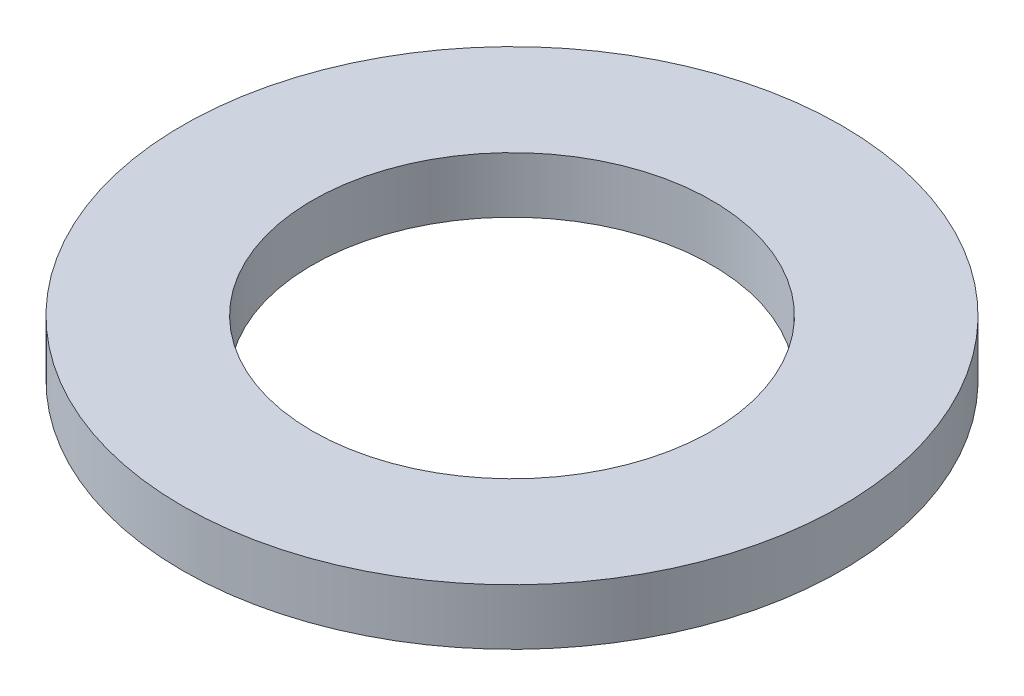
SolidWorks part; units mm, degrees
ref_plane "Front Plane" through (0, 0, 0) normal (0, 0, 1) x (1, 0, 0)
ref_plane "Top Plane" through (0, 0, 0) normal (0, 1, 0) x (1, 0, 0)
ref_plane "Right Plane" through (0, 0, 0) normal (1, 0, 0) x (0, 0, -1)
sketch "Sketch1" plane through (0, 0, 0) normal (0, 1, 0) x (1, 0, 0)
  circle A0 centre (0, 0) radius 82.5
  dimension "FLANGE_OD" = 165
extrude "Boss-Extrude1" add sketch "Sketch1" along normal blind 14
sketch "Sketch2" plane through (0, 0, 0) normal (0, 1, 0) x (1, 0, 0)
  circle A0 centre (0, 0) radius 50
  dimension "BORE_D" = 100
extrude "Cut-Extrude1" cut sketch "Sketch2" along normal through all
sketch "Sketch3" plane through (0, 14, 0) normal (0, 1, 0) x (1, 0, 0)
  circle A0 centre (0, 0) radius 37.3771 construction
  circle A1 centre (-37.3771, 0) radius 2.3532
  dimension "BOLT_D" = 4.7065
  dimension "BOLT_PCD" = 74.7543
extrude "Cut-Extrude2" cut sketch "Sketch3" against normal blind 9.458 rebuild error yes
pattern_circular "CirPattern1" count 3 over 360 rebuild error yes
